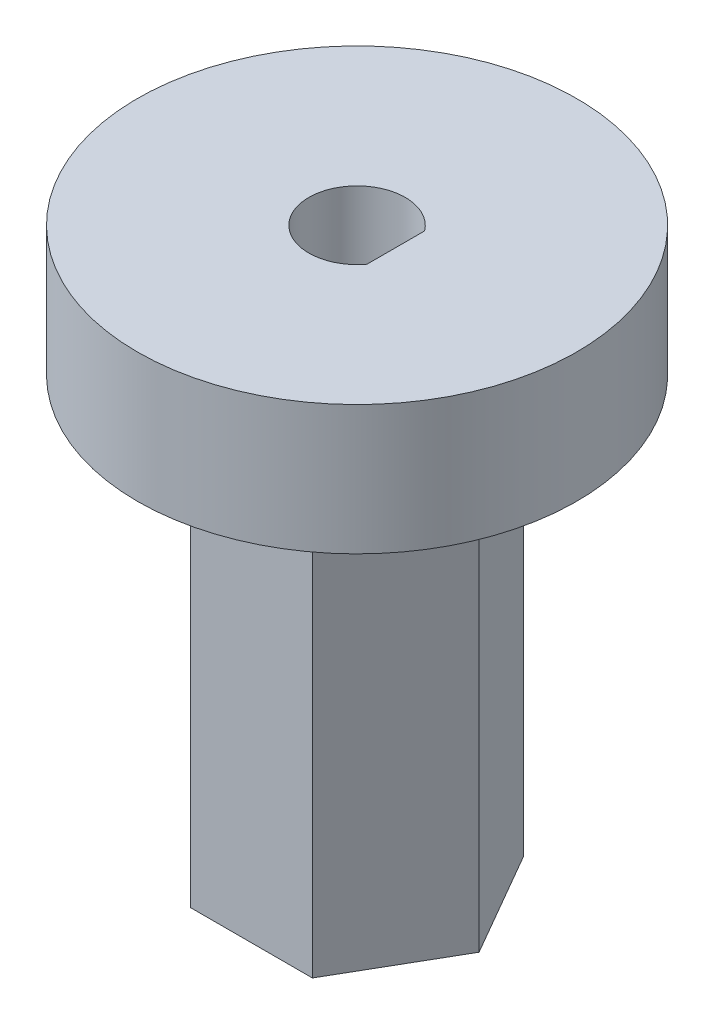
SolidWorks part; units mm, degrees
ref_plane "Front Plane" through (0, 0, 0) normal (0, 0, 1) x (1, 0, 0)
ref_plane "Top Plane" through (0, 0, 0) normal (0, 1, 0) x (1, 0, 0)
ref_plane "Right Plane" through (0, 0, 0) normal (1, 0, 0) x (0, 0, -1)
sketch "Sketch1" plane through (0, 0, 0) normal (0, 1, 0) x (1, 0, 0)
  line L0 (2.0146, -1.4999) -> (2.0146, 1.4999)
  line L2 (-3.175, -5.4993) -> (3.175, -5.4993)
  line L3 (3.175, -5.4993) -> (6.35, 0)
  line L4 (6.35, 0) -> (3.175, 5.4993)
  line L5 (3.175, 5.4993) -> (-3.175, 5.4993)
  line L6 (-3.175, 5.4993) -> (-6.35, 0)
  line L7 (-6.35, 0) -> (-3.175, -5.4993)
  arc A0 (2.0146, 1.4999) -> (2.0146, -1.4999) centre (0, 0) ccw
  circle A1 centre (0, 0) radius 5.4993 construction
  circle A2 centre (0, 0) radius 11.43
  dimension "D2" = 2.5116
  dimension "D4" = 22.86
  dimension "D1" = 2.9997
  dimension "D3" = 12.7
extrude "Boss-Extrude1" add sketch "Sketch1" along normal blind 6.731 contours A2 L7 L6 L5 L4 L3 L2 | L6 L7 L2 L3 L4 L5 A0 L0 region at (-4.617, 0, 2.6656) region at (-11.1067, 0, 0)
extrude "Boss-Extrude2" add sketch "Sketch1<3>" against normal blind 22.86 contours L6 L7 L2 L3 L4 L5 A0 L0 region at (-4.617, 0, 2.6656)
sketch "Sketch1<3>" plane through (0, 0, 0) normal (0, 1, 0) x (1, 0, 0) same geometry as "Sketch1"
